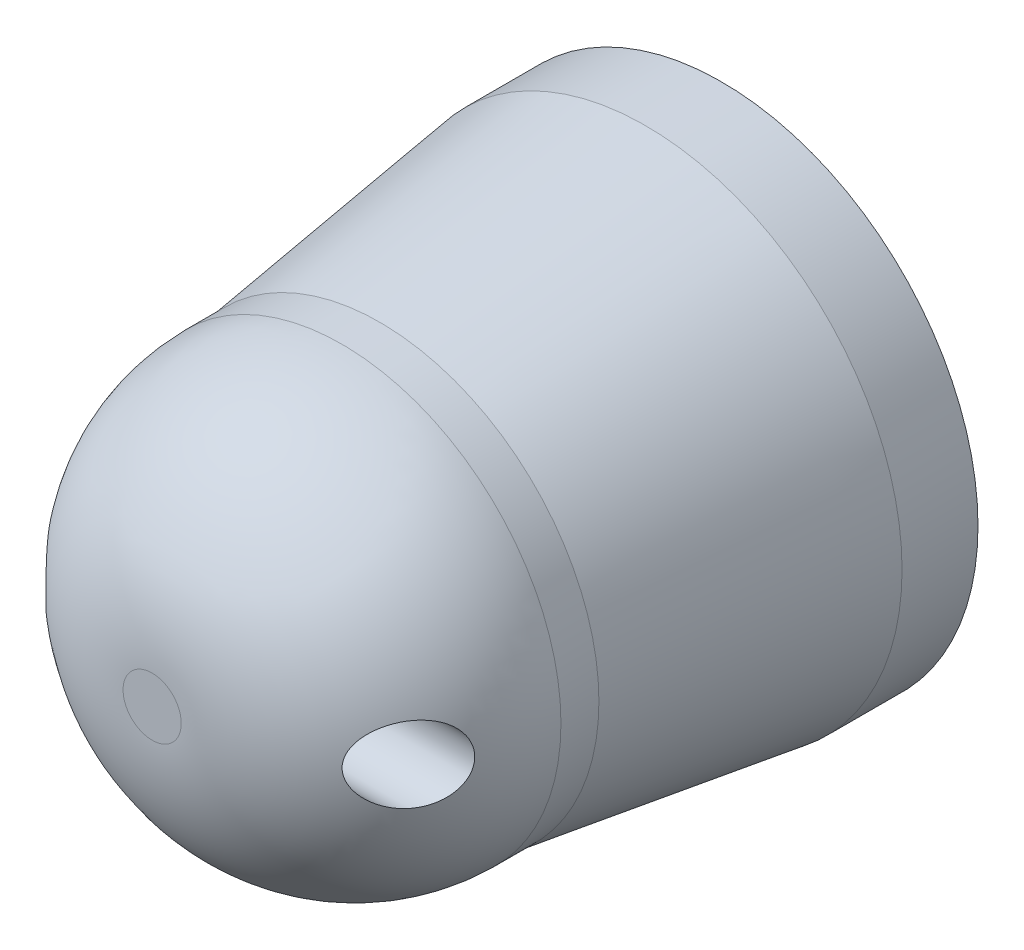
SolidWorks part; units mm, degrees
material "7075-O (SS)"
ref_plane "Front Plane" through (0, 0, 0) normal (0, 0, 1) x (1, 0, 0)
ref_plane "Top Plane" through (0, 0, 0) normal (0, 1, 0) x (1, 0, 0)
ref_plane "Right Plane" through (0, 0, 0) normal (1, 0, 0) x (0, 0, -1)
sketch "Sketch1" plane through (0, 0, 0) normal (0, 1, 0) x (1, 0, 0)
  line L0 (0, 0) -> (0, 51.5561) construction
  line L1 (0, 0) -> (-0.7662, 0)
  line L2 (0, 15) -> (-6.75, 15)
  line L3 (-6.75, 15) -> (-6.75, 13)
  line L4 (-6.75, 13) -> (-5.7662, 6)
  line L5 (0, 0) -> (0, 15)
  line L6 (-5.7662, 6) -> (-5.7662, 5)
  arc A0 (-0.7662, 0) -> (-5.7662, 5) centre (-0.7662, 5) cw
  point P4 (-6.75, 13)
  point P9 (0, 4)
  point P10 (0, 6)
  dimension "D1" = 5
revolve "Revolve1" add sketch "Sketch1" angle 360 about L0
hole_wizard "Ø6.0mm Dowel Hole1" positions "Sketch3" profile "Sketch2" hole size "Ø6.0" standard "GB"
sketch "Sketch3" plane through (0, 0, -15) normal (0, 0, -1) x (-1, 0, 0)
  point P0 (0, 0)
sketch "Sketch2" plane through (0, 0, -15) normal (1, 0, 0) x (0, 1, 0)
  line L0 (0, 0) -> (0, 10.8026)
  line L1 (0, 10.8026) -> (3, 9)
  line L2 (3, 9) -> (3, 0)
  line L5 (3, 0) -> (0, 0)
  line L10 (0, 10.8026) -> (-3, 9) construction
  line L11 (0, -6.35) -> (0, 107.95) construction
  dimension "Hole Dia." = 6
  dimension "Hole Depth" = 9
  dimension "Drill Angle" = 118
sketch "Sketch4" plane through (0, 0, 0) normal (1, 0, 0) x (0, 0, -1)
  circle A0 centre (2.1032, 0) radius 1
extrude "Cut-Extrude1" cut sketch "Sketch4" against normal blind 10 and the other way blind 10
